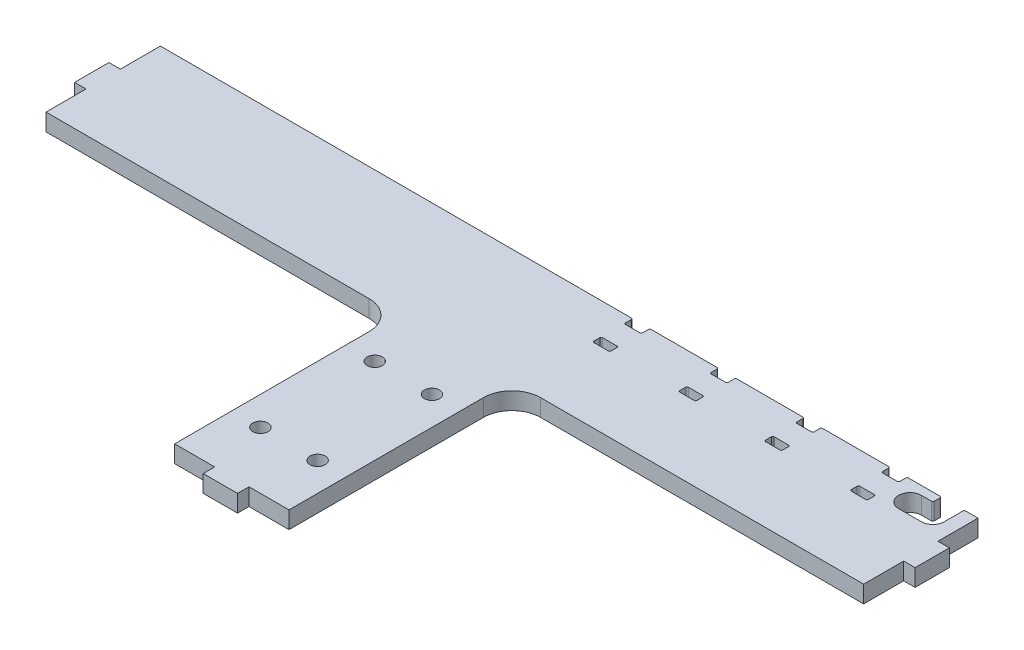
SolidWorks part; units mm, degrees
ref_plane "Front Plane" through (0, 0, 0) normal (0, 0, 1) x (1, 0, 0)
ref_plane "Top Plane" through (0, 0, 0) normal (0, 1, 0) x (1, 0, 0)
ref_plane "Right Plane" through (0, 0, 0) normal (1, 0, 0) x (0, 0, -1)
sketch "Sketch1" plane through (0, 0, 0) normal (0, 1, 0) x (1, 0, 0)
  line L0 (0, 24.5) -> (0, -24.5) construction
  line L1 (-71.5, 24.5) -> (71.5, 24.5)
  line L2 (-71.5, 24.5) -> (-71.5, -24.5)
  line L3 (-71.5, -24.5) -> (71.5, -24.5)
  line L4 (71.5, 24.5) -> (71.5, -24.5)
  line L5 (-71.5, 24.5) -> (71.5, -24.5) construction
  line L6 (-71.5, -24.5) -> (71.5, 24.5) construction
  line L7 (-71.5, 27.5) -> (-71.5, 21.5)
  line L8 (-3, -24.5) -> (3, -24.5)
  line L9 (-3, -24.5) -> (-3, -26.5)
  line L10 (-3, -26.5) -> (3, -26.5)
  line L11 (3, -24.5) -> (3, -26.5)
  line L12 (-3, -24.5) -> (3, -26.5) construction
  line L13 (-3, -26.5) -> (3, -24.5) construction
  line L14 (71.5, 27.5) -> (73.5, 27.5)
  line L15 (71.5, 27.5) -> (71.5, 21.5)
  line L16 (71.5, 21.5) -> (73.5, 21.5)
  line L17 (73.5, 27.5) -> (73.5, 21.5)
  line L18 (71.5, 27.5) -> (73.5, 21.5) construction
  line L19 (71.5, 21.5) -> (73.5, 27.5) construction
  line L20 (-71.5, 34.5) -> (71.5, 34.5)
  line L21 (-71.5, 34.5) -> (-71.5, 14.5)
  line L22 (-71.5, 14.5) -> (71.5, 14.5)
  line L23 (71.5, 34.5) -> (71.5, 14.5)
  line L24 (-71.5, 34.5) -> (71.5, 14.5) construction
  line L25 (-71.5, 14.5) -> (71.5, 34.5) construction
  line L26 (-10, -24.5) -> (10, -24.5)
  line L27 (-10, -24.5) -> (-10, 24.5)
  line L28 (-10, 24.5) -> (10, 24.5)
  line L29 (10, -24.5) -> (10, 24.5)
  line L30 (-10, -24.5) -> (10, 24.5) construction
  line L31 (-10, 24.5) -> (10, -24.5) construction
  line L32 (-71.5, 27.5) -> (-73.5, 27.5)
  line L33 (-73.5, 27.5) -> (-73.5, 21.5)
  line L34 (-71.5, 21.5) -> (-73.5, 21.5)
  point P0 (0, 0)
  point P8 (0, -25.5)
  point P13 (72.5, 24.5)
  point P22 (0, 0)
  dimension "D1" = 49
  dimension "D2" = 143
  dimension "D3" = 2
  dimension "D4" = 6
  dimension "D5" = 20
extrude "Boss-Extrude1" add sketch "Sketch1" along normal blind 3 contours L34 L2 L7 L32 L33 | L23 L20 L21 L7 L1 L15 | L22 L27 L1 L2 | L22 L29 L1 L27 | L29 L22 L4 L1 | L17 L14 L15 L4 L16 | L3 L29 L22 L27 | L11 L3 L9 L10 region at (0, 0, -29.5) region at (-40.75, 0, -19.5) region at (-72.5, 0, -24.5) region at (0, 0, -19.5) region at (40.75, 0, -19.5) region at (0, 0, 5) region at (72.5, 0, -24.5) region at (0, 0, 25.5)
fillet "Fillet1" radius 5 2 edges at (-10, 1.5, -14.5) (10, 1.5, -14.5)
sketch "Sketch2" plane through (0, 3, 0) normal (0, 1, 0) x (1, 0, 0)
  line L0 (0, -26.5) -> (0, 34.5) construction
  line L1 (-3, -26.5) -> (3, -26.5) construction
  line L2 (-71.5, 34.5) -> (71.5, 34.5) construction
  line L3 (-10, -24.5) -> (-3, -24.5) construction
  circle A0 centre (-5, -14.5) radius 1.325
  circle A1 centre (-5, 5.5) radius 1.325
  circle A2 centre (5, 5.5) radius 1.325
  circle A3 centre (5, -14.5) radius 1.325
  point P12 (0, 0)
  dimension "D3" = 2.65
  dimension "D1" = 10
  dimension "D2" = 10
  dimension "D4" = 20
extrude "Cut-Extrude1" cut sketch "Sketch2" against normal up to next
sketch "Sketch3" plane through (0, 3, 0) normal (0, 1, 0) x (1, 0, 0)
  line L0 (73.5, 24.5) -> (-73.5, 24.5) construction
  line L1 (73.5, 27.5) -> (73.5, 21.5) construction
  line L2 (-73.5, 27.5) -> (-73.5, 21.5) construction
  line L3 (59.1, 33) -> (67.1, 33) construction
  line L4 (56.1, 34.5) -> (59.1, 34.5)
  line L5 (56.1, 34.5) -> (56.1, 33.25)
  line L6 (56.35, 33) -> (58.85, 33)
  line L7 (59.1, 34.5) -> (59.1, 33.25)
  line L8 (69.1, 34.5) -> (69.1, 14.5) construction
  line L9 (-71.5, 34.5) -> (71.5, 34.5) construction
  line L10 (15, 14.5) -> (71.5, 14.5) construction
  line L11 (71.5, 21.5) -> (71.5, 14.5) construction
  line L12 (63.1, 33) -> (67.1, 33)
  line L13 (63.1, 29) -> (67.1, 29)
  line L14 (63.1, 31) -> (67.1, 31) construction
  line L15 (65.1, 31) -> (65.1, 34.5)
  line L16 (69.1, 31) -> (69.1, 34.5)
  line L17 (65.1, 34.5) -> (69.1, 34.5)
  line L18 (56.1, 27.75) -> (56.1, 28.75)
  line L19 (56.35, 27.5) -> (58.85, 27.5)
  line L20 (59.1, 27.75) -> (59.1, 28.75)
  line L21 (56.35, 29) -> (58.85, 29)
  line L22 (41.35, 27.5) -> (43.85, 27.5)
  line L23 (44.1, 27.75) -> (44.1, 28.75)
  line L24 (41.35, 29) -> (43.85, 29)
  line L25 (41.1, 27.75) -> (41.1, 28.75)
  line L26 (41.35, 33) -> (43.85, 33)
  line L27 (44.1, 34.5) -> (44.1, 33.25)
  line L28 (41.1, 34.5) -> (44.1, 34.5)
  line L29 (41.1, 34.5) -> (41.1, 33.25)
  line L30 (26.35, 27.5) -> (28.85, 27.5)
  line L31 (29.1, 27.75) -> (29.1, 28.75)
  line L32 (26.35, 29) -> (28.85, 29)
  line L33 (26.1, 27.75) -> (26.1, 28.75)
  line L34 (26.35, 33) -> (28.85, 33)
  line L35 (29.1, 34.5) -> (29.1, 33.25)
  line L36 (26.1, 34.5) -> (29.1, 34.5)
  line L37 (26.1, 34.5) -> (26.1, 33.25)
  line L38 (11.35, 27.5) -> (13.85, 27.5)
  line L39 (14.1, 27.75) -> (14.1, 28.75)
  line L40 (11.35, 29) -> (13.85, 29)
  line L41 (11.1, 27.75) -> (11.1, 28.75)
  line L42 (11.35, 33) -> (13.85, 33)
  line L43 (14.1, 34.5) -> (14.1, 33.25)
  line L44 (11.1, 34.5) -> (14.1, 34.5)
  line L45 (11.1, 34.5) -> (11.1, 33.25)
  circle A0 centre (67.1, 31) radius 2
  circle A1 centre (63.1, 31) radius 2
  arc A2 (58.85, 33) -> (59.1, 33.25) centre (58.85, 33.25) ccw
  arc A3 (56.1, 33.25) -> (56.35, 33) centre (56.35, 33.25) ccw
  arc A4 (56.1, 27.75) -> (56.35, 27.5) centre (56.35, 27.75) ccw
  arc A5 (58.85, 27.5) -> (59.1, 27.75) centre (58.85, 27.75) ccw
  arc A6 (59.1, 28.75) -> (58.85, 29) centre (58.85, 28.75) ccw
  arc A7 (56.1, 28.75) -> (56.35, 29) centre (56.35, 28.75) cw
  arc A8 (43.85, 27.5) -> (44.1, 27.75) centre (43.85, 27.75) ccw
  arc A9 (44.1, 28.75) -> (43.85, 29) centre (43.85, 28.75) ccw
  arc A10 (41.1, 28.75) -> (41.35, 29) centre (41.35, 28.75) cw
  arc A11 (41.1, 27.75) -> (41.35, 27.5) centre (41.35, 27.75) ccw
  arc A12 (43.85, 33) -> (44.1, 33.25) centre (43.85, 33.25) ccw
  arc A13 (41.1, 33.25) -> (41.35, 33) centre (41.35, 33.25) ccw
  arc A14 (28.85, 27.5) -> (29.1, 27.75) centre (28.85, 27.75) ccw
  arc A15 (29.1, 28.75) -> (28.85, 29) centre (28.85, 28.75) ccw
  arc A16 (26.1, 28.75) -> (26.35, 29) centre (26.35, 28.75) cw
  arc A17 (26.1, 27.75) -> (26.35, 27.5) centre (26.35, 27.75) ccw
  arc A18 (28.85, 33) -> (29.1, 33.25) centre (28.85, 33.25) ccw
  arc A19 (26.1, 33.25) -> (26.35, 33) centre (26.35, 33.25) ccw
  arc A20 (13.85, 27.5) -> (14.1, 27.75) centre (13.85, 27.75) ccw
  arc A21 (14.1, 28.75) -> (13.85, 29) centre (13.85, 28.75) ccw
  arc A22 (11.1, 28.75) -> (11.35, 29) centre (11.35, 28.75) cw
  arc A23 (11.1, 27.75) -> (11.35, 27.5) centre (11.35, 27.75) ccw
  arc A24 (13.85, 33) -> (14.1, 33.25) centre (13.85, 33.25) ccw
  arc A25 (11.1, 33.25) -> (11.35, 33) centre (11.35, 33.25) ccw
  point P38 (56.1, 33)
  point P41 (56.1, 27.5)
  point P44 (59.1, 27.5)
  point P47 (59.1, 29)
  point P50 (56.1, 29)
  dimension "D4" = 4
  dimension "D6" = 0.25
  dimension "D1" = 1.5
  dimension "D2" = 3
  dimension "D3" = 2.4
  dimension "D5" = 10
  dimension "D8" = 15
  dimension "D7" = 4
extrude "Cut-Extrude3" cut sketch "Sketch3" against normal up to next contours A0 | A0 L12 L15 | A1 L15 L12 | A1 L13 A0 | A1 | L5 A3 L6 A2 L7 L29 | A7 L18 A4 L19 A5 L20 A6 L21 | L29 A13 L26 A12 L27 | L25 A11 L22 A8 L23 A9 L24 A10 | L37 A19 L34 A18 L35 L29 | L33 A17 L30 A14 L31 A15 L32 A16 | A0 L16 L29 L15 L12 | L41 A23 L38 A20 L39 A21 L40 A22 | L45 A25 L42 A24 L43 L29 region at (57.6, 3, -33.7542) region at (64.6533, 3, -32.5533) region at (63.1, 3, -31) region at (67.2944, 3, -33.6002) region at (65.5467, 3, -32.5533) region at (67.1, 3, -31) region at (65.1, 3, -29.4467) region at (57.6, 3, -28.25) region at (42.6, 3, -28.25) region at (42.6, 3, -33.7542) region at (27.6, 3, -28.25) region at (27.6, 3, -33.7542) region at (12.6, 3, -28.25) region at (12.6, 3, -33.7542)
fillet "Fillet2" radius 0.25 11 edges at (26.1, 1.5, -34.5) (29.1, 1.5, -34.5) (41.1, 1.5, -34.5) (44.1, 1.5, -34.5) (56.1, 1.5, -34.5) (59.1, 1.5, -34.5) (69.1, 1.5, -34.5) (65.1, 1.5, -34.5) (65.1, 1.5, -33) (14.1, 1.5, -34.5) (11.1, 1.5, -34.5)
